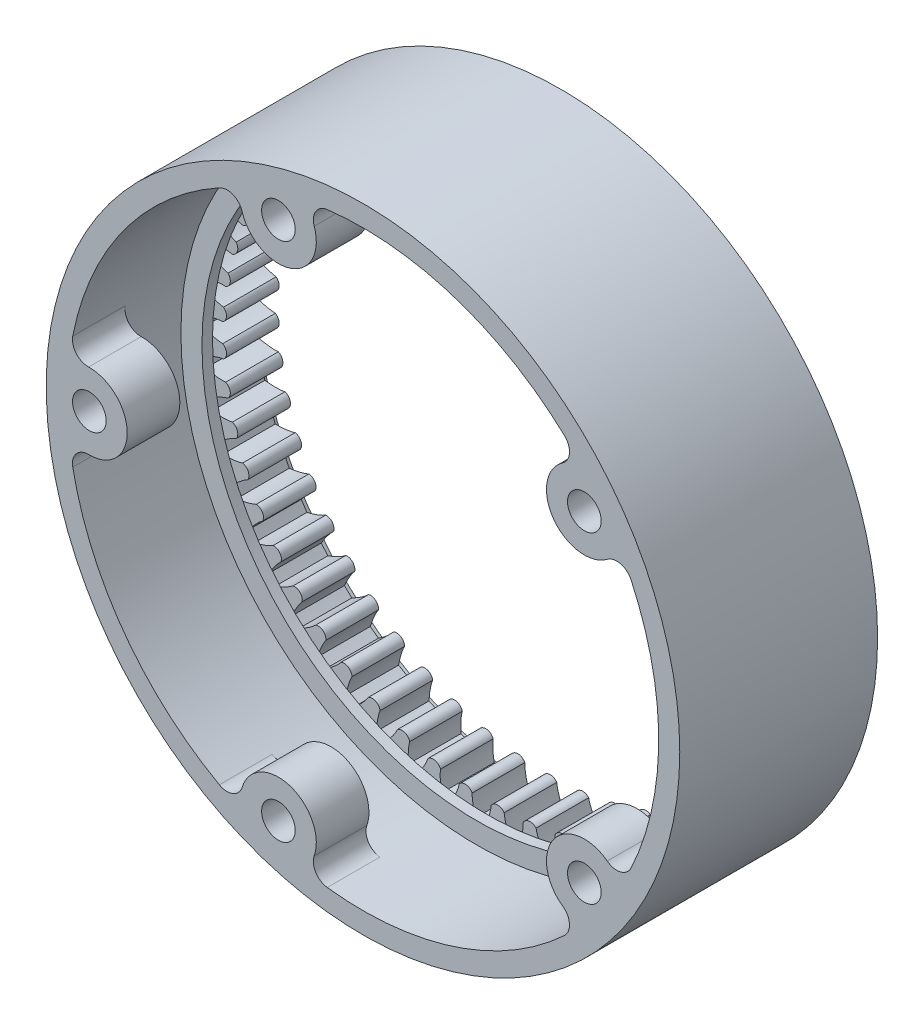
SolidWorks part; units mm, degrees
ref_plane "Front Plane" through (0, 0, 0) normal (0, 0, 1) x (1, 0, 0)
ref_plane "Top Plane" through (0, 0, 0) normal (0, 1, 0) x (1, 0, 0)
ref_plane "Right Plane" through (0, 0, 0) normal (1, 0, 0) x (0, 0, -1)
ref_plane "Plane1" through (0, 0, 15.8) normal (0, 0, 1) x (1, 0, 0)
sketch "Sketch1" plane through (0, 0, 15.8) normal (0, 0, 1) x (1, 0, 0)
  line L0 (4, 29.833) -> (4, 34.1)
  line L1 (-4, 34.1) -> (-4, 29.833)
  line L2 (-29.833, 4) -> (-34.1, 4)
  line L3 (-34.1, -4) -> (-29.833, -4)
  line L4 (-4, -29.833) -> (-4, -34.1)
  line L5 (4, -34.1) -> (4, -29.833)
  line L6 (29.833, -4) -> (34.1, -4)
  line L7 (34.1, 4) -> (29.833, 4)
  arc A0 (29.833, 4) -> (4, 29.833) centre (0, 0) ccw
  arc A1 (4, 34.1) -> (-4, 34.1) centre (0, 34.1) ccw
  arc A2 (-4, 29.833) -> (-29.833, 4) centre (0, 0) ccw
  arc A3 (-34.1, 4) -> (-34.1, -4) centre (-34.1, 0) ccw
  arc A4 (-29.833, -4) -> (-4, -29.833) centre (0, 0) ccw
  arc A5 (-4, -34.1) -> (4, -34.1) centre (0, -34.1) ccw
  arc A6 (4, -29.833) -> (29.833, -4) centre (0, 0) ccw
  arc A7 (34.1, -4) -> (34.1, 4) centre (34.1, 0) ccw
extrude "Boss-Extrude1" add sketch "Sketch1" against normal blind 1.9
sketch "Sketch2" plane through (0, 0, 13.9) normal (0, 0, -1) x (-1, 0, 0)
  line L0 (-29.833, -4) -> (-34.1, -4)
  line L1 (-34.1, 4) -> (-29.833, 4)
  arc A0 (-29.833, 4) -> (-29.833, -4) centre (0, 0) cw
  arc A1 (-34.1, -4) -> (-34.1, 4) centre (-34.1, 0) cw
extrude "Boss-Extrude2" add sketch "Sketch2" along normal blind 12.9
sketch "Sketch3" plane through (0, 0, 1) normal (0, 0, -1) x (-1, 0, 0)
  circle A0 centre (0, 0) radius 29
extrude "Cut-Extrude1" cut sketch "Sketch3" against normal blind 1
sketch "Sketch4" plane through (0, 0, 2) normal (0, 0, -1) x (-1, 0, 0)
  arc A0 (-27.9958, 0.4841) -> (-27.9958, -0.4838) centre (0, 0.0002) ccw
  arc A1 (-26.1243, -0.905) -> (-26.0527, -2.1336) centre (-26.5165, -1.5442) cw
  arc A2 (-27.8627, -2.7692) -> (-27.7503, -3.7306) centre (0, 0.0002) ccw
  arc A3 (-25.8426, -3.9317) -> (-25.6288, -5.1437) centre (-26.1579, -4.6122) cw
  arc A4 (-27.3528, -5.9852) -> (-27.1295, -6.927) centre (0, 0.0002) ccw
  arc A5 (-25.2114, -6.9052) -> (-24.8584, -8.0843) centre (-25.4456, -7.6177) cw
  arc A6 (-26.4729, -9.1202) -> (-26.1419, -10.0297) centre (0, 0.0002) ccw
  arc A7 (-24.2392, -9.7854) -> (-23.7517, -10.9155) centre (-24.3891, -10.5203) cw
  arc A8 (-25.2351, -12.1318) -> (-24.8007, -12.9968) centre (0, 0.0002) ccw
  arc A9 (-22.9393, -12.5333) -> (-22.3239, -13.5991) centre (-23.0029, -13.2806) cw
  arc A10 (-23.6561, -14.9794) -> (-23.1242, -15.7881) centre (0, 0.0002) ccw
  arc A11 (-21.3291, -15.1116) -> (-20.5942, -16.0988) centre (-21.3055, -15.8612) cw
  arc A12 (-21.7571, -17.6244) -> (-21.1349, -18.3659) centre (0, 0.0002) ccw
  arc A13 (-19.4306, -17.4856) -> (-18.5859, -18.3808) centre (-19.3201, -18.2274) cw
  arc A14 (-19.5639, -20.0311) -> (-18.8598, -20.6953) centre (0, 0.0002) ccw
  arc A15 (-17.2692, -19.6231) -> (-16.3264, -20.4142) centre (-17.0733, -20.3471) cw
  arc A16 (-17.1061, -22.1669) -> (-16.3297, -22.7449) centre (0, 0.0002) ccw
  arc A17 (-14.8743, -21.4953) -> (-13.846, -22.1716) centre (-14.5957, -22.1916) cw
  arc A18 (-14.417, -24.0029) -> (-13.5788, -24.4869) centre (0, 0.0002) ccw
  arc A19 (-12.2783, -23.0767) -> (-11.1784, -23.6291) centre (-11.9207, -23.736) cw
  arc A20 (-11.5329, -25.5143) -> (-10.6442, -25.8977) centre (0, 0.0002) ccw
  arc A21 (-9.5162, -24.3461) -> (-8.3596, -24.767) centre (-9.0845, -24.9594) cw
  arc A22 (-8.4929, -26.6807) -> (-7.5656, -26.9583) centre (0, 0.0002) ccw
  arc A23 (-6.6254, -25.2863) -> (-5.4278, -25.5701) centre (-6.1254, -25.8453) cw
  arc A24 (-5.338, -27.4863) -> (-4.3848, -27.6543) centre (0, 0.0002) ccw
  arc A25 (-3.645, -25.8844) -> (-2.4226, -26.0273) centre (-3.0835, -26.3817) cw
  arc A26 (-2.1109, -27.9201) -> (-1.1446, -27.9764) centre (0, 0.0002) ccw
  arc A27 (-0.6153, -26.1326) -> (0.6154, -26.1326) centre (0.0001, -26.5613) cw
  arc A28 (1.1447, -27.9764) -> (2.111, -27.9201) centre (0, 0.0002) ccw
  arc A29 (2.4226, -26.0273) -> (3.6451, -25.8844) centre (3.0836, -26.3817) cw
  arc A30 (4.3849, -27.6543) -> (5.3381, -27.4863) centre (0, 0.0002) ccw
  arc A31 (5.4279, -25.5701) -> (6.6255, -25.2862) centre (6.1255, -25.8453) cw
  arc A32 (7.5657, -26.9583) -> (8.4929, -26.6807) centre (0, 0.0002) ccw
  arc A33 (8.3597, -24.7671) -> (9.5162, -24.3461) centre (9.0846, -24.9594) cw
  arc A34 (10.6442, -25.8977) -> (11.533, -25.5143) centre (0, 0.0002) ccw
  arc A35 (11.1785, -23.6291) -> (12.2783, -23.0767) centre (11.9208, -23.736) cw
  arc A36 (13.5788, -24.4869) -> (14.4171, -24.0029) centre (0, 0.0002) ccw
  arc A37 (13.8461, -22.1716) -> (14.8744, -21.4952) centre (14.5958, -22.1916) cw
  arc A38 (16.3298, -22.7449) -> (17.1062, -22.1669) centre (0, 0.0002) ccw
  arc A39 (16.3265, -20.4142) -> (17.2693, -19.6231) centre (17.0734, -20.3471) cw
  arc A40 (18.8599, -20.6953) -> (19.5639, -20.0311) centre (0, 0.0002) ccw
  arc A41 (18.586, -18.3808) -> (19.4306, -17.4856) centre (19.3202, -18.2274) cw
  arc A42 (21.135, -18.3659) -> (21.7572, -17.6245) centre (0, 0.0002) ccw
  arc A43 (20.5943, -16.0988) -> (21.3292, -15.1116) centre (21.3056, -15.8612) cw
  arc A44 (23.1243, -15.7881) -> (23.6561, -14.9794) centre (0, 0.0002) ccw
  arc A45 (22.324, -13.5991) -> (22.9394, -12.5332) centre (23.0029, -13.2805) cw
  arc A46 (24.8008, -12.9968) -> (25.2352, -12.1318) centre (0, 0.0002) ccw
  arc A47 (23.7518, -10.9155) -> (24.2393, -9.7854) centre (24.3892, -10.5203) cw
  arc A48 (26.142, -10.0297) -> (26.473, -9.1202) centre (0, 0.0002) ccw
  arc A49 (24.8585, -8.0843) -> (25.2114, -6.9052) centre (25.4456, -7.6177) cw
  arc A50 (27.1296, -6.927) -> (27.3528, -5.9854) centre (0, 0.0002) ccw
  arc A51 (25.6289, -5.1439) -> (25.8426, -3.9319) centre (26.1579, -4.6123) cw
  arc A52 (27.7504, -3.7308) -> (27.8627, -2.7693) centre (0, 0.0002) ccw
  arc A53 (26.0528, -2.1336) -> (26.1244, -0.905) centre (26.5166, -1.5442) cw
  arc A54 (27.9959, -0.4838) -> (27.9959, 0.4841) centre (0, 0.0002) ccw
  arc A55 (26.1244, 0.9053) -> (26.0528, 2.134) centre (26.5166, 1.5446) cw
  arc A56 (27.8627, 2.7696) -> (27.7504, 3.731) centre (0, 0.0002) ccw
  arc A57 (25.8427, 3.9321) -> (25.6289, 5.1441) centre (26.158, 4.6125) cw
  arc A58 (27.3528, 5.9856) -> (27.1296, 6.9274) centre (0, 0.0002) ccw
  arc A59 (25.2115, 6.9056) -> (24.8584, 8.0847) centre (25.4456, 7.6181) cw
  arc A60 (26.473, 9.1206) -> (26.142, 10.0301) centre (0, 0.0002) ccw
  arc A61 (24.2393, 9.7858) -> (23.7518, 10.9159) centre (24.3892, 10.5207) cw
  arc A62 (25.2352, 12.1322) -> (24.8008, 12.9972) centre (0, 0.0002) ccw
  arc A63 (22.9394, 12.5336) -> (22.324, 13.5995) centre (23.0029, 13.2809) cw
  arc A64 (23.6561, 14.9798) -> (23.1243, 15.7885) centre (0, 0.0002) ccw
  arc A65 (21.3292, 15.112) -> (20.5942, 16.0992) centre (21.3056, 15.8616) cw
  arc A66 (21.7572, 17.6248) -> (21.135, 18.3663) centre (0, 0.0002) ccw
  arc A67 (19.4306, 17.486) -> (18.586, 18.3812) centre (19.3201, 18.2278) cw
  arc A68 (19.564, 20.0315) -> (18.8599, 20.6957) centre (0, 0.0002) ccw
  arc A69 (17.2693, 19.6235) -> (16.3264, 20.4146) centre (17.0734, 20.3475) cw
  arc A70 (17.1062, 22.1673) -> (16.3298, 22.7453) centre (0, 0.0002) ccw
  arc A71 (14.8744, 21.4956) -> (13.8461, 22.1719) centre (14.5958, 22.192) cw
  arc A72 (14.4171, 24.0033) -> (13.5788, 24.4873) centre (0, 0.0002) ccw
  arc A73 (12.2783, 23.0771) -> (11.1785, 23.6294) centre (11.9208, 23.7364) cw
  arc A74 (11.533, 25.5147) -> (10.6443, 25.8981) centre (0, 0.0002) ccw
  arc A75 (9.5162, 24.3465) -> (8.3597, 24.7674) centre (9.0846, 24.9598) cw
  arc A76 (8.493, 26.6811) -> (7.5657, 26.9587) centre (0, 0.0002) ccw
  arc A77 (6.6255, 25.2866) -> (5.4279, 25.5704) centre (6.1255, 25.8457) cw
  arc A78 (5.3381, 27.4866) -> (4.3849, 27.6547) centre (0, 0.0002) ccw
  arc A79 (3.6451, 25.8848) -> (2.4226, 26.0277) centre (3.0836, 26.382) cw
  arc A80 (2.111, 27.9205) -> (1.1447, 27.9768) centre (0, 0.0002) ccw
  arc A81 (0.6154, 26.133) -> (-0.6153, 26.1329) centre (0, 26.5616) cw
  arc A82 (-1.1446, 27.9768) -> (-2.1109, 27.9205) centre (0, 0.0002) ccw
  arc A83 (-2.4226, 26.0277) -> (-3.645, 25.8848) centre (-3.0836, 26.382) cw
  arc A84 (-4.3848, 27.6547) -> (-5.338, 27.4867) centre (0, 0.0002) ccw
  arc A85 (-5.4278, 25.5705) -> (-6.6254, 25.2866) centre (-6.1255, 25.8457) cw
  arc A86 (-7.5656, 26.9587) -> (-8.4929, 26.6811) centre (0, 0.0002) ccw
  arc A87 (-8.3596, 24.7674) -> (-9.5162, 24.3465) centre (-9.0845, 24.9598) cw
  arc A88 (-10.6442, 25.8981) -> (-11.5329, 25.5147) centre (0, 0.0002) ccw
  arc A89 (-11.1784, 23.6295) -> (-12.2782, 23.0771) centre (-11.9207, 23.7364) cw
  arc A90 (-13.5788, 24.4873) -> (-14.417, 24.0033) centre (0, 0.0002) ccw
  arc A91 (-13.846, 22.172) -> (-14.8743, 21.4956) centre (-14.5957, 22.192) cw
  arc A92 (-16.3297, 22.7453) -> (-17.1061, 22.1673) centre (0, 0.0002) ccw
  arc A93 (-16.3264, 20.4146) -> (-17.2692, 19.6235) centre (-17.0733, 20.3474) cw
  arc A94 (-18.8598, 20.6957) -> (-19.5639, 20.0315) centre (0, 0.0002) ccw
  arc A95 (-18.5859, 18.3812) -> (-19.4305, 17.486) centre (-19.3201, 18.2278) cw
  arc A96 (-21.1349, 18.3663) -> (-21.7571, 17.6248) centre (0, 0.0002) ccw
  arc A97 (-20.5942, 16.0992) -> (-21.3291, 15.112) centre (-21.3055, 15.8616) cw
  arc A98 (-23.1242, 15.7885) -> (-23.6561, 14.9798) centre (0, 0.0002) ccw
  arc A99 (-22.3239, 13.5995) -> (-22.9393, 12.5336) centre (-23.0029, 13.2809) cw
  arc A100 (-24.8007, 12.9972) -> (-25.2351, 12.1322) centre (0, 0.0002) ccw
  arc A101 (-23.7518, 10.9159) -> (-24.2392, 9.7858) centre (-24.3891, 10.5206) cw
  arc A102 (-26.1419, 10.0301) -> (-26.4729, 9.1206) centre (0, 0.0002) ccw
  arc A103 (-24.8584, 8.0847) -> (-25.2113, 6.9056) centre (-25.4456, 7.6181) cw
  arc A104 (-27.1295, 6.9274) -> (-27.3528, 5.9856) centre (0, 0.0002) ccw
  arc A105 (-25.6289, 5.1441) -> (-25.8425, 3.9321) centre (-26.1579, 4.6125) cw
  arc A106 (-27.7503, 3.731) -> (-27.8627, 2.7696) centre (0, 0.0002) ccw
  arc A107 (-26.0527, 2.134) -> (-26.1243, 0.9053) centre (-26.5165, 1.5446) cw
  ellipse E0 centre (-27.7817, 0.0692) end of major axis (-29.975, 0.8686) minor radius 0.5928 (-27.9958, -0.4838) -> (-26.1243, -0.905) ccw
  ellipse E1 centre (-27.576, -3.281) end of major axis (-29.647, -4.3182) minor radius 0.586 (-26.0527, -2.1336) -> (-27.8627, -2.7692) ccw
  ellipse E2 centre (-27.6019, -3.1565) end of major axis (-29.8731, -2.6172) minor radius 0.5928 (-27.7503, -3.7306) -> (-25.8426, -3.9317) ccw
  ellipse E3 centre (-27.0086, -6.4602) end of major axis (-28.9452, -7.7308) minor radius 0.586 (-25.6288, -5.1437) -> (-27.3528, -5.9852) ccw
  ellipse E4 centre (-27.0488, -6.3396) end of major axis (-29.3673, -6.0675) minor radius 0.5928 (-27.1295, -6.927) -> (-25.2114, -6.9052) ccw
  ellipse E5 centre (-26.076, -9.552) end of major axis (-27.8519, -11.0388) minor radius 0.586 (-24.8584, -8.0843) -> (-26.4729, -9.1202) ccw
  ellipse E6 centre (-26.1299, -9.4369) end of major axis (-28.4643, -9.4359) minor radius 0.5928 (-26.1419, -10.0297) -> (-24.2392, -9.7854) ccw
  ellipse E7 centre (-24.7907, -12.5146) end of major axis (-23.1993, -10.8317) minor radius 0.586 (-23.7517, -10.9155) -> (-25.2351, -12.1318) ccw
  ellipse E8 centre (-24.8576, -12.4066) end of major axis (-27.1764, -12.6766) minor radius 0.5928 (-24.8007, -12.9968) -> (-22.9393, -12.5333) ccw
  ellipse E9 centre (-23.1702, -15.308) end of major axis (-21.785, -13.4517) minor radius 0.586 (-22.3239, -13.5991) -> (-23.6561, -14.9794) ccw
  ellipse E10 centre (-23.2492, -15.2085) end of major axis (-25.5209, -15.7458) minor radius 0.5928 (-23.1242, -15.7881) -> (-21.3291, -15.1116) ccw
  ellipse E11 centre (-21.2363, -17.8944) end of major axis (-20.076, -15.8898) minor radius 0.586 (-20.5942, -16.0988) -> (-21.7571, -17.6244) ccw
  ellipse E12 centre (-21.3264, -17.8047) end of major axis (-23.5204, -18.6022) minor radius 0.5928 (-21.1349, -18.3659) -> (-19.4306, -17.4856) ccw
  ellipse E13 centre (-19.0153, -20.2388) end of major axis (-18.0955, -18.1131) minor radius 0.586 (-18.5859, -18.3808) -> (-19.5639, -20.0311) ccw
  ellipse E14 centre (-19.1151, -20.1602) end of major axis (-21.2017, -21.2069) minor radius 0.5928 (-18.8598, -20.6953) -> (-17.2692, -19.6231) ccw
  ellipse E15 centre (-16.5371, -22.3095) end of major axis (-15.8703, -20.0914) minor radius 0.586 (-16.3264, -20.4142) -> (-17.1061, -22.1669) ccw
  ellipse E16 centre (-16.6454, -22.243) end of major axis (-18.5964, -23.5249) minor radius 0.5928 (-16.3297, -22.7449) -> (-14.8743, -21.4953) ccw
  ellipse E17 centre (-13.8353, -24.0785) end of major axis (-13.4306, -21.798) minor radius 0.586 (-13.846, -22.1716) -> (-14.417, -24.0029) ccw
  ellipse E18 centre (-13.9506, -24.025) end of major axis (-15.7395, -25.5247) minor radius 0.5928 (-13.5788, -24.4869) -> (-12.2783, -23.0767) ccw
  ellipse E19 centre (-10.9464, -25.5219) end of major axis (-10.8091, -23.2098) minor radius 0.586 (-11.1784, -23.6291) -> (-11.5329, -25.5143) ccw
  ellipse E20 centre (-11.0671, -25.4821) end of major axis (-9.4644, -23.7849) minor radius 0.5928 (-10.6442, -25.8977) -> (-9.5162, -24.3461) ccw
  ellipse E21 centre (-7.9094, -26.6201) end of major axis (-8.0415, -24.3077) minor radius 0.586 (-8.3596, -24.767) -> (-8.4929, -26.6807) ccw
  ellipse E22 centre (-8.034, -26.5947) end of major axis (-6.6391, -24.7228) minor radius 0.5928 (-7.5656, -26.9583) -> (-6.6254, -25.2863) ccw
  ellipse E23 centre (-4.7655, -27.3584) end of major axis (-5.1652, -25.0769) minor radius 0.586 (-5.4278, -25.5701) -> (-5.338, -27.4863) ccw
  ellipse E24 centre (-4.8922, -27.3475) end of major axis (-3.724, -25.3264) minor radius 0.5928 (-4.3848, -27.6543) -> (-3.645, -25.8844) ccw
  ellipse E25 centre (-1.5572, -27.7266) end of major axis (-2.219, -25.507) minor radius 0.586 (-2.4226, -26.0273) -> (-2.1109, -27.9201) ccw
  ellipse E26 centre (-1.6842, -27.7306) end of major axis (-0.7586, -25.5875) minor radius 0.5928 (-1.1446, -27.9764) -> (-0.6153, -26.1326) ccw
  ellipse E27 centre (1.6722, -27.7199) end of major axis (0.7572, -25.5921) minor radius 0.586 (0.6154, -26.1326) -> (1.1447, -27.9764) ccw
  ellipse E28 centre (1.5465, -27.7386) end of major axis (2.217, -25.5026) minor radius 0.5928 (2.111, -27.9201) -> (2.4226, -26.0273) ccw
  ellipse E29 centre (4.879, -27.3384) end of major axis (6.0349, -29.3456) minor radius 0.586 (3.6451, -25.8844) -> (4.3849, -27.6543) ccw
  ellipse E30 centre (4.7563, -27.3715) end of major axis (5.1627, -25.0727) minor radius 0.5928 (5.3381, -27.4863) -> (5.4279, -25.5701) ccw
  ellipse E31 centre (8.0199, -26.5871) end of major axis (6.6388, -24.7277) minor radius 0.586 (6.6255, -25.2862) -> (7.5657, -26.9583) ccw
  ellipse E32 centre (7.9018, -26.6342) end of major axis (8.0386, -24.3038) minor radius 0.5928 (8.4929, -26.6807) -> (8.3597, -24.7671) ccw
  ellipse E33 centre (11.0522, -25.4763) end of major axis (9.4646, -23.7898) minor radius 0.586 (9.5162, -24.3461) -> (10.6442, -25.8977) ccw
  ellipse E34 centre (10.9405, -25.5368) end of major axis (10.8058, -23.2063) minor radius 0.5928 (11.533, -25.5143) -> (11.1785, -23.6291) ccw
  ellipse E35 centre (13.9351, -24.0209) end of major axis (15.7078, -25.5118) minor radius 0.586 (12.2783, -23.0767) -> (13.5788, -24.4869) ccw
  ellipse E36 centre (13.8312, -24.094) end of major axis (13.4268, -21.7949) minor radius 0.5928 (14.4171, -24.0029) -> (13.8461, -22.1716) ccw
  ellipse E37 centre (16.6296, -22.2407) end of major axis (14.6959, -20.9658) minor radius 0.586 (14.8744, -21.4952) -> (16.3298, -22.7449) ccw
  ellipse E38 centre (16.5348, -22.3254) end of major axis (15.8663, -20.0888) minor radius 0.5928 (17.1062, -22.1669) -> (16.3265, -20.4142) ccw
  ellipse E39 centre (19.0992, -20.1598) end of major axis (17.0305, -19.118) minor radius 0.586 (17.2693, -19.6231) -> (18.8599, -20.6953) ccw
  ellipse E40 centre (19.0149, -20.2549) end of major axis (18.0912, -18.111) minor radius 0.5928 (19.5639, -20.0311) -> (18.586, -18.3808) ccw
  ellipse E41 centre (21.3105, -17.8062) end of major axis (19.1348, -17.0116) minor radius 0.586 (19.4306, -17.4856) -> (21.135, -18.3659) ccw
  ellipse E42 centre (21.2378, -17.9104) end of major axis (20.0715, -15.8883) minor radius 0.5928 (21.7572, -17.6245) -> (20.5943, -16.0988) ccw
  ellipse E43 centre (23.2336, -15.2118) end of major axis (20.9804, -14.6751) minor radius 0.586 (21.3292, -15.1116) -> (23.1243, -15.7881) ccw
  ellipse E44 centre (23.1735, -15.3238) end of major axis (21.7803, -13.4507) minor radius 0.5928 (23.6561, -14.9794) -> (22.324, -13.5991) ccw
  ellipse E45 centre (24.8425, -12.4117) end of major axis (22.5422, -12.1402) minor radius 0.586 (22.9394, -12.5332) -> (24.8008, -12.9968) ccw
  ellipse E46 centre (24.7958, -12.5299) end of major axis (23.1946, -10.8312) minor radius 0.5928 (25.2352, -12.1318) -> (23.7518, -10.9155) ccw
  ellipse E47 centre (26.1154, -9.4437) end of major axis (23.7992, -9.4412) minor radius 0.586 (24.2393, -9.7854) -> (26.142, -10.0297) ccw
  ellipse E48 centre (26.0828, -9.5666) end of major axis (24.2952, -8.0652) minor radius 0.5928 (26.473, -9.1202) -> (24.8585, -8.0843) ccw
  ellipse E49 centre (27.0352, -6.3481) end of major axis (24.7344, -6.6144) minor radius 0.586 (25.2114, -6.9052) -> (27.1296, -6.927) ccw
  ellipse E50 centre (27.017, -6.4741) end of major axis (25.0672, -5.1904) minor radius 0.5928 (27.3528, -5.9854) -> (25.6289, -5.1439) ccw
  ellipse E51 centre (27.5894, -3.1668) end of major axis (25.335, -3.6984) minor radius 0.586 (25.8426, -3.9319) -> (27.7504, -3.7308) ccw
  ellipse E52 centre (27.5859, -3.2936) end of major axis (25.5003, -2.245) minor radius 0.5928 (27.8627, -2.7693) -> (26.0528, -2.1336) ccw
  ellipse E53 centre (27.7705, 0.0578) end of major axis (25.5931, -0.732) minor radius 0.586 (26.1244, -0.905) -> (27.9959, -0.4838) ccw
  ellipse E54 centre (27.7818, -0.0688) end of major axis (29.9751, -0.8682) minor radius 0.5928 (27.9959, 0.4841) -> (26.1244, 0.9053) ccw
  ellipse E55 centre (27.576, 3.2813) end of major axis (25.505, 2.2442) minor radius 0.586 (26.0528, 2.134) -> (27.8627, 2.7696) ccw
  ellipse E56 centre (27.602, 3.1569) end of major axis (25.3307, 3.6963) minor radius 0.5928 (27.7504, 3.731) -> (25.8427, 3.9321) ccw
  ellipse E57 centre (27.0087, 6.4605) end of major axis (25.0721, 5.1899) minor radius 0.586 (25.6289, 5.1441) -> (27.3528, 5.9856) ccw
  ellipse E58 centre (27.0489, 6.34) end of major axis (24.7304, 6.612) minor radius 0.5928 (27.1296, 6.9274) -> (25.2115, 6.9056) ccw
  ellipse E59 centre (26.076, 9.5524) end of major axis (24.3001, 8.0655) minor radius 0.586 (24.8584, 8.0847) -> (26.473, 9.1206) ccw
  ellipse E60 centre (26.13, 9.4373) end of major axis (23.7956, 9.4383) minor radius 0.5928 (26.142, 10.0301) -> (24.2393, 9.7858) ccw
  ellipse E61 centre (24.7908, 12.515) end of major axis (26.3821, 14.198) minor radius 0.586 (23.7518, 10.9159) -> (25.2352, 12.1322) ccw
  ellipse E62 centre (24.8577, 12.407) end of major axis (22.539, 12.137) minor radius 0.5928 (24.8008, 12.9972) -> (22.9394, 12.5336) ccw
  ellipse E63 centre (23.1703, 15.3084) end of major axis (24.5555, 17.1648) minor radius 0.586 (22.324, 13.5995) -> (23.6561, 14.9798) ccw
  ellipse E64 centre (23.2493, 15.2089) end of major axis (25.521, 15.7462) minor radius 0.5928 (23.1243, 15.7885) -> (21.3292, 15.112) ccw
  ellipse E65 centre (21.2364, 17.8948) end of major axis (22.3968, 19.8994) minor radius 0.586 (20.5942, 16.0992) -> (21.7572, 17.6248) ccw
  ellipse E66 centre (21.3265, 17.8051) end of major axis (19.1325, 17.0077) minor radius 0.5928 (21.135, 18.3663) -> (19.4306, 17.486) ccw
  ellipse E67 centre (19.0154, 20.2392) end of major axis (19.9352, 22.365) minor radius 0.586 (18.586, 18.3812) -> (19.564, 20.0315) ccw
  ellipse E68 centre (19.1152, 20.1606) end of major axis (17.0287, 19.1138) minor radius 0.5928 (18.8599, 20.6957) -> (17.2693, 19.6235) ccw
  ellipse E69 centre (16.5372, 22.3099) end of major axis (17.204, 24.5281) minor radius 0.586 (16.3264, 20.4146) -> (17.1062, 22.1673) ccw
  ellipse E70 centre (16.6455, 22.2434) end of major axis (14.6946, 20.9615) minor radius 0.5928 (16.3298, 22.7453) -> (14.8744, 21.4956) ccw
  ellipse E71 centre (13.8354, 24.0789) end of major axis (14.2402, 26.3595) minor radius 0.586 (13.8461, 22.1719) -> (14.4171, 24.0033) ccw
  ellipse E72 centre (13.9507, 24.0254) end of major axis (12.1617, 22.5257) minor radius 0.5928 (13.5788, 24.4873) -> (12.2783, 23.0771) ccw
  ellipse E73 centre (10.9465, 25.5223) end of major axis (11.0837, 27.8344) minor radius 0.586 (11.1785, 23.6294) -> (11.533, 25.5147) ccw
  ellipse E74 centre (11.0672, 25.4825) end of major axis (12.6699, 27.1798) minor radius 0.5928 (10.6443, 25.8981) -> (9.5162, 24.3465) ccw
  ellipse E75 centre (7.9095, 26.6205) end of major axis (7.7774, 28.933) minor radius 0.586 (8.3597, 24.7674) -> (8.493, 26.6811) ccw
  ellipse E76 centre (8.034, 26.595) end of major axis (9.4289, 28.4669) minor radius 0.5928 (7.5657, 26.9587) -> (6.6255, 25.2866) ccw
  ellipse E77 centre (4.7656, 27.3588) end of major axis (4.366, 29.6402) minor radius 0.586 (5.4279, 25.5704) -> (5.3381, 27.4866) ccw
  ellipse E78 centre (4.8922, 27.3479) end of major axis (6.0603, 29.369) minor radius 0.5928 (4.3849, 27.6547) -> (3.6451, 25.8848) ccw
  ellipse E79 centre (1.5573, 27.727) end of major axis (0.8954, 29.9467) minor radius 0.586 (2.4226, 26.0277) -> (2.111, 27.9205) ccw
  ellipse E80 centre (1.6843, 27.7309) end of major axis (2.6099, 29.874) minor radius 0.5928 (1.1447, 27.9768) -> (0.6154, 26.133) ccw
  ellipse E81 centre (-1.6722, 27.7203) end of major axis (-2.5872, 29.8481) minor radius 0.586 (-0.6153, 26.1329) -> (-1.1446, 27.9768) ccw
  ellipse E82 centre (-1.5464, 27.739) end of major axis (-0.8759, 29.975) minor radius 0.5928 (-2.1109, 27.9205) -> (-2.4226, 26.0277) ccw
  ellipse E83 centre (-4.879, 27.3387) end of major axis (-6.0348, 29.3459) minor radius 0.586 (-3.645, 25.8848) -> (-4.3848, 27.6547) ccw
  ellipse E84 centre (-4.7563, 27.3719) end of major axis (-4.3499, 29.6706) minor radius 0.5928 (-5.338, 27.4867) -> (-5.4278, 25.5705) ccw
  ellipse E85 centre (-8.0198, 26.5875) end of major axis (-9.4008, 28.4469) minor radius 0.586 (-6.6254, 25.2866) -> (-7.5656, 26.9587) ccw
  ellipse E86 centre (-7.9018, 26.6346) end of major axis (-7.765, 28.965) minor radius 0.5928 (-8.4929, 26.6811) -> (-8.3596, 24.7674) ccw
  ellipse E87 centre (-11.0522, 25.4767) end of major axis (-12.6397, 27.1632) minor radius 0.586 (-9.5162, 24.3465) -> (-10.6442, 25.8981) ccw
  ellipse E88 centre (-10.9404, 25.5372) end of major axis (-11.0751, 27.8677) minor radius 0.5928 (-11.5329, 25.5147) -> (-11.1784, 23.6295) ccw
  ellipse E89 centre (-13.9351, 24.0213) end of major axis (-12.1624, 22.5305) minor radius 0.586 (-12.2782, 23.0771) -> (-13.5788, 24.4873) ccw
  ellipse E90 centre (-13.8311, 24.0944) end of major axis (-14.2354, 26.3935) minor radius 0.5928 (-14.417, 24.0033) -> (-13.846, 22.172) ccw
  ellipse E91 centre (-16.6295, 22.2411) end of major axis (-18.5633, 23.5161) minor radius 0.586 (-14.8743, 21.4956) -> (-16.3297, 22.7453) ccw
  ellipse E92 centre (-16.5347, 22.3258) end of major axis (-17.2032, 24.5624) minor radius 0.5928 (-17.1061, 22.1673) -> (-16.3264, 20.4146) ccw
  ellipse E93 centre (-19.0991, 20.1602) end of major axis (-21.1678, 21.202) minor radius 0.586 (-17.2692, 19.6235) -> (-18.8598, 20.6957) ccw
  ellipse E94 centre (-19.0148, 20.2553) end of major axis (-19.9384, 22.3992) minor radius 0.5928 (-19.5639, 20.0315) -> (-18.5859, 18.3812) ccw
  ellipse E95 centre (-21.3104, 17.8066) end of major axis (-23.486, 18.6012) minor radius 0.586 (-19.4305, 17.486) -> (-21.1349, 18.3663) ccw
  ellipse E96 centre (-21.2377, 17.9108) end of major axis (-22.404, 19.933) minor radius 0.5928 (-21.7571, 17.6248) -> (-20.5942, 16.0992) ccw
  ellipse E97 centre (-23.2335, 15.2122) end of major axis (-25.4867, 15.7489) minor radius 0.586 (-21.3291, 15.112) -> (-23.1242, 15.7885) ccw
  ellipse E98 centre (-23.1734, 15.3242) end of major axis (-24.5665, 17.1973) minor radius 0.5928 (-23.6561, 14.9798) -> (-22.3239, 13.5995) ccw
  ellipse E99 centre (-24.8424, 12.4121) end of major axis (-27.1426, 12.6836) minor radius 0.586 (-22.9393, 12.5336) -> (-24.8007, 12.9972) ccw
  ellipse E100 centre (-24.7957, 12.5303) end of major axis (-26.3969, 14.229) minor radius 0.5928 (-25.2351, 12.1322) -> (-23.7518, 10.9159) ccw
  ellipse E101 centre (-26.1153, 9.4441) end of major axis (-28.4316, 9.4467) minor radius 0.586 (-24.2392, 9.7858) -> (-26.1419, 10.0301) ccw
  ellipse E102 centre (-26.0827, 9.5669) end of major axis (-27.8703, 11.0683) minor radius 0.5928 (-26.4729, 9.1206) -> (-24.8584, 8.0847) ccw
  ellipse E103 centre (-27.0351, 6.3485) end of major axis (-29.336, 6.0821) minor radius 0.586 (-25.2113, 6.9056) -> (-27.1295, 6.9274) ccw
  ellipse E104 centre (-27.0169, 6.4742) end of major axis (-28.9667, 7.7579) minor radius 0.5928 (-27.3528, 5.9856) -> (-25.6289, 5.1441) ccw
  ellipse E105 centre (-27.5893, 3.1669) end of major axis (-29.8437, 2.6353) minor radius 0.586 (-25.8425, 3.9321) -> (-27.7503, 3.731) ccw
  ellipse E106 centre (-27.5859, 3.294) end of major axis (-29.6715, 4.3426) minor radius 0.5928 (-27.8627, 2.7696) -> (-26.0527, 2.134) ccw
  ellipse E107 centre (-27.7704, -0.0574) end of major axis (-29.9478, -0.8472) minor radius 0.586 (-26.1243, 0.9053) -> (-27.9958, 0.4841) ccw
  point P3 (-27.7818, 0.069)
  point P4 (-29.975, 0.8684)
  point P5 (-27.5788, 0.626)
  point P6 (-27.9958, -0.484)
  point P7 (-26.1244, -0.9051)
  point P8 (-27.0757, -0.7649)
  point P9 (-28.4879, 0.9028)
  point P18 (-27.576, -3.2812)
  point P19 (-29.647, -4.3183)
  point P20 (-27.8384, -2.7572)
  point P21 (-26.0527, -2.1338)
  point P22 (-27.8627, -2.7694)
  point P23 (-26.9809, -2.3834)
  point P24 (-28.1711, -4.1789)
  point P32 (-27.6019, -3.1567)
  point P33 (-29.8732, -2.6174)
  point P34 (-27.465, -2.58)
  point P35 (-27.7503, -3.7308)
  point P36 (-25.8426, -3.9319)
  point P37 (-26.8038, -3.903)
  point P38 (-28.4001, -2.4105)
  point P47 (-27.0086, -6.4603)
  point P48 (-28.9452, -7.731)
  point P49 (-27.3301, -5.9704)
  point P50 (-25.6289, -5.1439)
  point P51 (-27.3528, -5.9854)
  point P52 (-26.5218, -5.4996)
  point P53 (-27.4955, -7.4211)
  point P61 (-27.0488, -6.3398)
  point P62 (-29.3673, -6.0677)
  point P63 (-26.9797, -5.751)
  point P64 (-27.1296, -6.9272)
  point P65 (-25.2114, -6.9054)
  point P66 (-26.1694, -6.9883)
  point P67 (-27.9282, -5.6913)
  point P76 (-26.076, -9.5522)
  point P77 (-27.852, -11.039)
  point P78 (-26.4521, -9.1029)
  point P79 (-24.8584, -8.0845)
  point P80 (-26.473, -9.1204)
  point P81 (-25.704, -8.5414)
  point P82 (-26.448, -10.5629)
  point P90 (-26.1299, -9.4371)
  point P91 (-28.4643, -9.436)
  point P92 (-26.1297, -8.8443)
  point P93 (-26.1419, -10.0299)
  point P94 (-24.2393, -9.7856)
  point P95 (-25.1812, -9.9791)
  point P96 (-27.0787, -8.895)
  point P105 (-24.7907, -12.5148)
  point P106 (-25.2165, -12.1122)
  point P107 (-23.1994, -10.8319)
  point P108 (-23.7518, -10.9157)
  point P109 (-25.2352, -12.132)
  point P110 (-24.5386, -11.4677)
  point P111 (-25.0429, -13.5619)
  point P119 (-24.8577, -12.4068)
  point P120 (-27.1764, -12.6767)
  point P121 (-24.9262, -11.8179)
  point P122 (-24.8008, -12.997)
  point P123 (-22.9394, -12.5335)
  point P124 (-23.8524, -12.835)
  point P125 (-25.8629, -11.9785)
  point P134 (-23.1702, -15.3082)
  point P135 (-23.6399, -14.9578)
  point P136 (-21.785, -13.4519)
  point P137 (-22.3239, -13.5993)
  point P138 (-23.6561, -14.9796)
  point P139 (-23.0413, -14.2389)
  point P140 (-23.2991, -16.3776)
  point P148 (-23.2492, -15.2087)
  point P149 (-25.521, -15.746)
  point P150 (-23.3857, -14.6318)
  point P151 (-23.1242, -15.7883)
  point P152 (-21.3292, -15.1118)
  point P153 (-22.2011, -15.5173)
  point P154 (-24.2974, -14.9)
  point P163 (-21.2364, -17.8946)
  point P164 (-21.7435, -17.6011)
  point P165 (-20.076, -15.89)
  point P166 (-20.5942, -16.099)
  point P167 (-21.7571, -17.6246)
  point P168 (-21.2325, -16.8176)
  point P169 (-21.2403, -18.9717)
  point P177 (-21.3264, -17.8049)
  point P178 (-23.5204, -18.6024)
  point P179 (-21.5289, -17.2478)
  point P180 (-21.135, -18.3661)
  point P181 (-19.4306, -17.4858)
  point P182 (-20.2495, -17.9898)
  point P183 (-22.4033, -17.62)
  point P192 (-19.0154, -20.239)
  point P193 (-19.5531, -20.0063)
  point P194 (-18.0956, -18.1133)
  point P195 (-18.586, -18.381)
  point P196 (-19.5639, -20.0313)
  point P197 (-19.1365, -19.1688)
  point P198 (-18.8942, -21.3092)
  point P206 (-19.1152, -20.1604)
  point P207 (-21.2018, -21.2071)
  point P208 (-19.381, -19.6305)
  point P209 (-18.8599, -20.6955)
  point P210 (-17.2692, -19.6233)
  point P211 (-18.0241, -20.219)
  point P212 (-20.2063, -20.1018)
  point P221 (-16.5372, -22.3097)
  point P222 (-17.0983, -22.141)
  point P223 (-15.8704, -20.0916)
  point P224 (-16.3264, -20.4144)
  point P225 (-17.1061, -22.1671)
  point P226 (-16.7818, -21.2608)
  point P227 (-16.2926, -23.3586)
  point P235 (-16.6455, -22.2432)
  point P236 (-18.5964, -23.5251)
  point P237 (-16.971, -21.7478)
  point P238 (-16.3298, -22.7451)
  point P239 (-14.8743, -21.4955)
  point P240 (-15.555, -22.1748)
  point P241 (-17.736, -22.3117)
  point P250 (-13.8354, -24.0787)
  point P251 (-14.4123, -23.9763)
  point P252 (-13.4306, -21.7981)
  point P253 (-13.846, -22.1717)
  point P254 (-14.417, -24.0031)
  point P255 (-14.2001, -23.0653)
  point P256 (-13.4706, -25.0922)
  point P264 (-13.9506, -24.0252)
  point P265 (-15.7396, -25.5249)
  point P266 (-14.3315, -23.5709)
  point P267 (-13.5788, -24.4871)
  point P268 (-12.2783, -23.0769)
  point P269 (-12.8755, -23.8306)
  point P270 (-15.0258, -24.2198)
  point P279 (-10.9464, -25.5221)
  point P280 (-11.5314, -25.4874)
  point P281 (-10.8092, -23.21)
  point P282 (-11.1784, -23.6293)
  point P283 (-11.5329, -25.5145)
  point P284 (-11.4263, -24.5578)
  point P285 (-10.4665, -26.4863)
  point P293 (-11.0672, -25.4823)
  point P294 (-11.4982, -25.0753)
  point P295 (-9.4644, -23.7851)
  point P296 (-10.6442, -25.8979)
  point P297 (-9.5162, -24.3463)
  point P298 (-10.0218, -25.1643)
  point P299 (-12.1125, -25.8004)
  point P308 (-7.9095, -26.6203)
  point P309 (-8.4945, -26.6537)
  point P310 (-8.0416, -24.3079)
  point P311 (-8.3597, -24.7672)
  point P312 (-8.4929, -26.6809)
  point P313 (-8.4981, -25.7183)
  point P314 (-7.3209, -27.5223)
  point P322 (-8.034, -26.5949)
  point P323 (-8.5094, -26.2406)
  point P324 (-6.6392, -24.723)
  point P325 (-7.5657, -26.9585)
  point P326 (-6.6254, -25.2865)
  point P327 (-7.0327, -26.1576)
  point P328 (-9.0353, -27.0322)
  point P337 (-4.7656, -27.3586)
  point P338 (-5.3428, -27.4597)
  point P339 (-5.1652, -25.0771)
  point P340 (-5.4278, -25.5702)
  point P341 (-5.338, -27.4865)
  point P342 (-5.4549, -26.531)
  point P343 (-4.0762, -28.1861)
  point P351 (-4.8922, -27.3477)
  point P352 (-5.4055, -27.0511)
  point P353 (-3.7241, -25.3266)
  point P354 (-4.3848, -27.6545)
  point P355 (-3.6451, -25.8846)
  point P356 (-3.9484, -26.7971)
  point P357 (-5.836, -27.8983)
  point P366 (-1.5572, -27.7268)
  point P367 (-2.1188, -27.8943)
  point P368 (-2.219, -25.5072)
  point P369 (-2.4226, -26.0275)
  point P370 (-2.1109, -27.9203)
  point P371 (-2.338, -26.9849)
  point P372 (-0.7765, -28.4688)
  point P380 (-1.6842, -27.7308)
  point P381 (-2.2285, -27.4957)
  point P382 (-0.7587, -25.5877)
  point P383 (-1.1447, -27.9766)
  point P384 (-0.6154, -26.1328)
  point P385 (-0.8108, -27.0743)
  point P386 (-2.5577, -28.3872)
  point P395 (1.6722, -27.7201)
  point P396 (1.1339, -27.9516)
  point P397 (0.7572, -25.5923)
  point P398 (0.6154, -26.1327)
  point P399 (1.1447, -27.9766)
  point P400 (0.8106, -27.0738)
  point P401 (2.5338, -28.3664)
  point P409 (1.5465, -27.7388)
  point P410 (0.9787, -27.5685)
  point P411 (2.217, -25.5028)
  point P412 (2.1109, -27.9203)
  point P413 (2.4226, -26.0275)
  point P414 (2.3379, -26.9854)
  point P415 (0.7551, -28.4922)
  point P424 (4.879, -27.3386)
  point P425 (4.3712, -27.631)
  point P426 (3.7231, -25.3314)
  point P427 (3.645, -25.8846)
  point P428 (4.3848, -27.6545)
  point P429 (3.9482, -26.7967)
  point P430 (5.8098, -27.8805)
  point P438 (4.7563, -27.3717)
  point P439 (4.1725, -27.2685)
  point P440 (5.1627, -25.0729)
  point P441 (5.338, -27.4865)
  point P442 (5.4278, -25.5703)
  point P443 (5.4549, -26.5315)
  point P444 (4.0577, -28.2119)
  point P453 (8.0198, -26.5873)
  point P454 (7.5494, -26.9367)
  point P455 (6.6388, -24.7279)
  point P456 (6.6254, -25.2864)
  point P457 (7.5657, -26.9585)
  point P458 (7.0324, -26.1571)
  point P459 (9.0073, -27.0175)
  point P467 (7.9018, -26.6344)
  point P468 (7.31, -26.5997)
  point P469 (8.0386, -24.304)
  point P470 (8.4929, -26.6809)
  point P471 (8.3597, -24.7673)
  point P472 (8.4981, -25.7188)
  point P473 (7.3055, -27.55)
  point P482 (11.0522, -25.4765)
  point P483 (10.6255, -25.8781)
  point P484 (9.4646, -23.7899)
  point P485 (9.5162, -24.3463)
  point P486 (10.6442, -25.8979)
  point P487 (10.0215, -25.1638)
  point P488 (12.0829, -25.7891)
  point P496 (10.9404, -25.537)
  point P497 (10.3486, -25.5712)
  point P498 (10.8058, -23.2065)
  point P499 (11.5329, -25.5145)
  point P500 (11.1784, -23.6293)
  point P501 (11.4264, -24.5584)
  point P502 (10.4545, -26.5156)
  point P511 (13.9351, -24.0211)
  point P512 (12.1625, -22.5303)
  point P513 (14.3123, -23.5727)
  point P514 (12.2783, -23.0769)
  point P515 (13.5788, -24.4871)
  point P516 (12.8751, -23.8303)
  point P517 (14.9951, -24.212)
  point P525 (13.8311, -24.0942)
  point P526 (13.2473, -24.1969)
  point P527 (13.4268, -21.7951)
  point P528 (14.417, -24.0031)
  point P529 (13.8461, -22.1718)
  point P530 (14.2002, -23.0658)
  point P531 (13.4621, -25.1227)
  point P540 (16.6296, -22.2409)
  point P541 (14.6958, -20.966)
  point P542 (16.9521, -21.7517)
  point P543 (14.8743, -21.4954)
  point P544 (16.3298, -22.7451)
  point P545 (15.5546, -22.1744)
  point P546 (17.7046, -22.3075)
  point P554 (16.5348, -22.3256)
  point P555 (15.9668, -22.4954)
  point P556 (15.8663, -20.089)
  point P557 (17.1061, -22.1671)
  point P558 (16.3264, -20.4144)
  point P559 (16.782, -21.2613)
  point P560 (16.2876, -23.3899)
  point P569 (19.0991, -20.16)
  point P570 (17.0305, -19.1181)
  point P571 (19.3627, -19.6366)
  point P572 (17.2692, -19.6233)
  point P573 (18.8599, -20.6955)
  point P574 (18.0237, -20.2187)
  point P575 (20.1746, -20.1012)
  point P583 (19.0148, -20.2551)
  point P584 (18.4704, -20.4896)
  point P585 (18.0912, -18.1112)
  point P586 (19.5639, -20.0313)
  point P587 (18.586, -18.381)
  point P588 (19.1368, -19.1693)
  point P589 (18.8929, -21.3409)
  point P598 (21.3104, -17.8064)
  point P599 (19.1348, -17.0118)
  point P600 (21.5115, -17.256)
  point P601 (19.4306, -17.4858)
  point P602 (21.135, -18.3661)
  point P603 (20.2491, -17.9896)
  point P604 (22.3718, -17.6232)
  point P612 (21.2377, -17.9106)
  point P613 (20.7242, -18.2068)
  point P614 (20.0714, -15.8885)
  point P615 (21.7571, -17.6246)
  point P616 (20.5942, -16.099)
  point P617 (21.2328, -16.818)
  point P618 (21.2427, -19.0033)
  point P627 (23.2335, -15.212)
  point P628 (20.9803, -14.6753)
  point P629 (23.3693, -14.642)
  point P630 (21.3292, -15.1118)
  point P631 (23.1242, -15.7883)
  point P632 (22.2006, -15.5172)
  point P633 (24.2665, -14.9068)
  point P641 (23.1734, -15.324)
  point P642 (22.6978, -15.6778)
  point P643 (21.7803, -13.4509)
  point P644 (23.6561, -14.9796)
  point P645 (22.324, -13.5993)
  point P646 (23.0417, -14.2393)
  point P647 (23.3052, -16.4087)
  point P656 (24.8424, -12.4119)
  point P657 (22.5422, -12.1404)
  point P658 (24.9111, -11.83)
  point P659 (22.9393, -12.5334)
  point P660 (24.8008, -12.997)
  point P661 (23.8519, -12.8349)
  point P662 (25.8329, -11.9889)
  point P670 (24.7957, -12.5301)
  point P671 (24.3644, -12.9367)
  point P672 (23.1945, -10.8314)
  point P673 (25.2352, -12.132)
  point P674 (23.7518, -10.9157)
  point P675 (24.539, -11.468)
  point P676 (25.0525, -13.5922)
  point P685 (26.1154, -9.4439)
  point P686 (23.7992, -9.4413)
  point P687 (26.116, -8.858)
  point P688 (24.2392, -9.7856)
  point P689 (26.1419, -10.0299)
  point P690 (25.1807, -9.9791)
  point P691 (27.0501, -8.9088)
  point P699 (26.0827, -9.5668)
  point P700 (24.2952, -8.0654)
  point P701 (26.464, -9.1128)
  point P702 (26.473, -9.1204)
  point P703 (24.8584, -8.0845)
  point P704 (25.7044, -8.5417)
  point P705 (26.4611, -10.5918)
  point P714 (27.0352, -6.3483)
  point P715 (24.7343, -6.6146)
  point P716 (26.9678, -5.7662)
  point P717 (25.2114, -6.9054)
  point P718 (27.1296, -6.9272)
  point P719 (26.1689, -6.9883)
  point P720 (27.9014, -5.7082)
  point P728 (27.017, -6.4741)
  point P729 (25.0672, -5.1904)
  point P730 (27.343, -5.9789)
  point P731 (27.3528, -5.9854)
  point P732 (25.6289, -5.1439)
  point P733 (26.5222, -5.4998)
  point P734 (27.5118, -7.4483)
  point P743 (27.5894, -3.1668)
  point P744 (25.335, -3.6984)
  point P745 (27.4549, -2.5964)
  point P746 (25.8426, -3.9319)
  point P747 (27.7503, -3.7308)
  point P748 (26.8033, -3.903)
  point P749 (28.3755, -2.4305)
  point P757 (27.5859, -3.2938)
  point P758 (25.5003, -2.2452)
  point P759 (27.8522, -2.7642)
  point P760 (27.8627, -2.7694)
  point P761 (26.0528, -2.1338)
  point P762 (26.9814, -2.3836)
  point P763 (28.1905, -4.204)
  point P772 (27.7705, 0.0576)
  point P773 (25.593, -0.7322)
  point P774 (27.5707, 0.6085)
  point P775 (26.1243, -0.9051)
  point P776 (27.9958, -0.484)
  point P777 (27.0752, -0.765)
  point P778 (28.4658, 0.8802)
  point P786 (27.7818, -0.069)
  point P787 (25.5885, 0.7304)
  point P788 (27.9848, 0.488)
  point P789 (27.9958, 0.484)
  point P790 (26.1244, 0.9051)
  point P791 (27.0757, 0.7649)
  point P792 (28.4879, -0.9028)
  point P801 (27.576, 3.2812)
  point P802 (25.505, 2.244)
  point P803 (27.3136, 3.8051)
  point P804 (26.0527, 2.1338)
  point P805 (27.8627, 2.7694)
  point P806 (26.9809, 2.3834)
  point P807 (28.1711, 4.1789)
  point P815 (27.6019, 3.1567)
  point P816 (25.3307, 3.6961)
  point P817 (27.7389, 3.7335)
  point P818 (27.7503, 3.7308)
  point P819 (25.8426, 3.9319)
  point P820 (26.8038, 3.903)
  point P821 (28.4001, 2.4105)
  point P830 (27.0086, 6.4603)
  point P831 (25.072, 5.1897)
  point P832 (26.6872, 6.9503)
  point P833 (25.6289, 5.1439)
  point P834 (27.3528, 5.9854)
  point P835 (26.5218, 5.4996)
  point P836 (27.4955, 7.4211)
  point P844 (27.0488, 6.3398)
  point P845 (24.7303, 6.6118)
  point P846 (27.1179, 6.9286)
  point P847 (27.1296, 6.9272)
  point P848 (25.2114, 6.9054)
  point P849 (26.1694, 6.9883)
  point P850 (27.9282, 5.6913)
  point P859 (26.076, 9.5522)
  point P860 (24.3, 8.0653)
  point P861 (25.6998, 10.0015)
  point P862 (24.8584, 8.0845)
  point P863 (26.473, 9.1204)
  point P864 (25.704, 8.5414)
  point P865 (26.448, 10.5629)
  point P873 (26.1299, 9.4371)
  point P874 (23.7955, 9.4381)
  point P875 (26.1302, 10.0299)
  point P876 (26.1419, 10.0299)
  point P877 (24.2393, 9.7856)
  point P878 (25.1812, 9.9791)
  point P879 (27.0787, 8.895)
  point P888 (24.7907, 12.5148)
  point P889 (24.365, 12.9174)
  point P890 (26.3821, 14.1978)
  point P891 (23.7518, 10.9157)
  point P892 (25.2352, 12.132)
  point P893 (24.5386, 11.4677)
  point P894 (25.0429, 13.5619)
  point P902 (24.8577, 12.4068)
  point P903 (22.5389, 12.1368)
  point P904 (24.7891, 12.9956)
  point P905 (24.8008, 12.997)
  point P906 (22.9394, 12.5335)
  point P907 (23.8524, 12.835)
  point P908 (25.8629, 11.9785)
  point P917 (23.1702, 15.3082)
  point P918 (22.7006, 15.6587)
  point P919 (24.5555, 17.1646)
  point P920 (22.3239, 13.5993)
  point P921 (23.6561, 14.9796)
  point P922 (23.0413, 14.2389)
  point P923 (23.2991, 16.3776)
  point P931 (23.2492, 15.2087)
  point P932 (20.9775, 14.6714)
  point P933 (23.1128, 15.7856)
  point P934 (23.1242, 15.7883)
  point P935 (21.3292, 15.1118)
  point P936 (22.2011, 15.5173)
  point P937 (24.2974, 14.9)
  point P946 (21.2364, 17.8946)
  point P947 (20.7292, 18.1882)
  point P948 (22.3967, 19.8992)
  point P949 (20.5942, 16.099)
  point P950 (21.7571, 17.6246)
  point P951 (21.2325, 16.8176)
  point P952 (21.2403, 18.9717)
  point P960 (21.3264, 17.8049)
  point P961 (19.1324, 17.0075)
  point P962 (21.1239, 18.3621)
  point P963 (21.135, 18.3661)
  point P964 (19.4306, 17.4858)
  point P965 (20.2495, 17.9898)
  point P966 (22.4033, 17.62)
  point P975 (19.0154, 20.239)
  point P976 (18.4776, 20.4717)
  point P977 (19.9351, 22.3648)
  point P978 (18.586, 18.381)
  point P979 (19.5639, 20.0313)
  point P980 (19.1365, 19.1688)
  point P981 (18.8942, 21.3092)
  point P989 (19.1152, 20.1604)
  point P990 (17.0286, 19.1136)
  point P991 (18.8494, 20.6903)
  point P992 (18.8599, 20.6955)
  point P993 (17.2692, 19.6233)
  point P994 (18.0241, 20.219)
  point P995 (20.2063, 20.1018)
  point P1004 (16.5372, 22.3097)
  point P1005 (15.976, 22.4784)
  point P1006 (17.204, 24.5279)
  point P1007 (16.3264, 20.4144)
  point P1008 (17.1061, 22.1671)
  point P1009 (16.7818, 21.2608)
  point P1010 (16.2926, 23.3586)
  point P1018 (16.6455, 22.2432)
  point P1019 (14.6945, 20.9613)
  point P1020 (16.3199, 22.7386)
  point P1021 (16.3298, 22.7451)
  point P1022 (14.8743, 21.4955)
  point P1023 (15.555, 22.1748)
  point P1024 (17.736, 22.3117)
  point P1033 (13.8354, 24.0787)
  point P1034 (13.2584, 24.1811)
  point P1035 (14.2401, 26.3593)
  point P1036 (13.846, 22.1717)
  point P1037 (14.417, 24.0031)
  point P1038 (14.2001, 23.0653)
  point P1039 (13.4706, 25.0922)
  point P1047 (13.9506, 24.0252)
  point P1048 (12.1617, 22.5255)
  point P1049 (13.5698, 24.4795)
  point P1050 (13.5788, 24.4871)
  point P1051 (12.2783, 23.0769)
  point P1052 (12.8755, 23.8306)
  point P1053 (15.0258, 24.2198)
  point P1062 (10.9464, 25.5221)
  point P1063 (10.3615, 25.5568)
  point P1064 (11.0837, 27.8342)
  point P1065 (11.1784, 23.6293)
  point P1066 (11.5329, 25.5145)
  point P1067 (11.4263, 24.5578)
  point P1068 (10.4665, 26.4863)
  point P1076 (11.0672, 25.4823)
  point P1077 (10.6361, 25.8894)
  point P1078 (12.6699, 27.1796)
  point P1079 (10.6442, 25.8979)
  point P1080 (9.5162, 24.3463)
  point P1081 (10.0218, 25.1643)
  point P1082 (12.1125, 25.8004)
  point P1091 (7.9095, 26.6203)
  point P1092 (7.3245, 26.5869)
  point P1093 (7.7774, 28.9328)
  point P1094 (8.3597, 24.7672)
  point P1095 (8.4929, 26.6809)
  point P1096 (8.4981, 25.7183)
  point P1097 (7.3209, 27.5223)
  point P1105 (8.034, 26.5949)
  point P1106 (7.5586, 26.9491)
  point P1107 (9.4288, 28.4667)
  point P1108 (7.5657, 26.9585)
  point P1109 (6.6254, 25.2865)
  point P1110 (7.0327, 26.1576)
  point P1111 (9.0353, 27.0322)
  point P1120 (4.7656, 27.3586)
  point P1121 (4.1884, 27.2575)
  point P1122 (4.3659, 29.64)
  point P1123 (5.4278, 25.5702)
  point P1124 (5.338, 27.4865)
  point P1125 (5.4549, 26.531)
  point P1126 (4.0762, 28.1861)
  point P1134 (4.8922, 27.3477)
  point P1135 (4.3789, 27.6444)
  point P1136 (6.0603, 29.3689)
  point P1137 (4.3848, 27.6545)
  point P1138 (3.6451, 25.8846)
  point P1139 (3.9484, 26.7971)
  point P1140 (5.836, 27.8983)
  point P1149 (1.5572, 27.7268)
  point P1150 (0.9957, 27.5594)
  point P1151 (0.8954, 29.9465)
  point P1152 (2.4226, 26.0275)
  point P1153 (2.1109, 27.9203)
  point P1154 (2.338, 26.9849)
  point P1155 (0.7765, 28.4688)
  point P1163 (1.6842, 27.7308)
  point P1164 (1.14, 27.9658)
  point P1165 (2.6098, 29.8738)
  point P1166 (1.1447, 27.9766)
  point P1167 (0.6154, 26.1328)
  point P1168 (0.8108, 27.0743)
  point P1169 (2.5577, 28.3872)
  point P1178 (-1.6722, 27.7201)
  point P1179 (-2.2105, 27.4886)
  point P1180 (-2.5872, 29.8479)
  point P1181 (-0.6154, 26.1327)
  point P1182 (-1.1447, 27.9766)
  point P1183 (-0.8106, 27.0738)
  point P1184 (-2.5338, 28.3664)
  point P1192 (-1.5465, 27.7388)
  point P1193 (-2.1143, 27.9091)
  point P1194 (-0.876, 29.9748)
  point P1195 (-2.1109, 27.9203)
  point P1196 (-2.4226, 26.0275)
  point P1197 (-2.3379, 26.9854)
  point P1198 (-0.7551, 28.4922)
  point P1207 (-4.879, 27.3386)
  point P1208 (-5.3868, 27.0461)
  point P1209 (-6.0349, 29.3458)
  point P1210 (-3.645, 25.8846)
  point P1211 (-4.3848, 27.6545)
  point P1212 (-3.9482, 26.7967)
  point P1213 (-5.8098, 27.8805)
  point P1221 (-4.7563, 27.3717)
  point P1222 (-5.3401, 27.4749)
  point P1223 (-4.3499, 29.6704)
  point P1224 (-5.338, 27.4865)
  point P1225 (-5.4278, 25.5703)
  point P1226 (-5.4549, 26.5315)
  point P1227 (-4.0577, 28.2119)
  point P1236 (-8.0198, 26.5873)
  point P1237 (-8.4902, 26.2379)
  point P1238 (-9.4009, 28.4467)
  point P1239 (-6.6254, 25.2864)
  point P1240 (-7.5657, 26.9585)
  point P1241 (-7.0324, 26.1571)
  point P1242 (-9.0073, 27.0175)
  point P1250 (-7.9018, 26.6344)
  point P1251 (-8.4936, 26.6692)
  point P1252 (-7.765, 28.9648)
  point P1253 (-8.4929, 26.6809)
  point P1254 (-8.3597, 24.7673)
  point P1255 (-8.4981, 25.7188)
  point P1256 (-7.3055, 27.55)
  point P1265 (-11.0522, 25.4765)
  point P1266 (-11.4789, 25.0748)
  point P1267 (-12.6398, 27.163)
  point P1268 (-9.5162, 24.3463)
  point P1269 (-10.6442, 25.8979)
  point P1270 (-10.0215, 25.1638)
  point P1271 (-12.0829, 25.7891)
  point P1279 (-10.9404, 25.537)
  point P1280 (-11.5323, 25.5028)
  point P1281 (-11.0751, 27.8675)
  point P1282 (-11.5329, 25.5145)
  point P1283 (-11.1784, 23.6293)
  point P1284 (-11.4264, 24.5584)
  point P1285 (-10.4545, 26.5156)
  point P1294 (-13.9351, 24.0211)
  point P1295 (-15.7078, 25.5119)
  point P1296 (-13.5579, 24.4696)
  point P1297 (-12.2783, 23.0769)
  point P1298 (-13.5788, 24.4871)
  point P1299 (-12.8751, 23.8303)
  point P1300 (-14.9951, 24.212)
  point P1308 (-13.8311, 24.0942)
  point P1309 (-14.415, 23.9915)
  point P1310 (-14.2355, 26.3933)
  point P1311 (-14.417, 24.0031)
  point P1312 (-13.8461, 22.1718)
  point P1313 (-14.2002, 23.0658)
  point P1314 (-13.4621, 25.1227)
  point P1323 (-16.6296, 22.2409)
  point P1324 (-18.5633, 23.5159)
  point P1325 (-16.307, 22.7301)
  point P1326 (-14.8743, 21.4954)
  point P1327 (-16.3298, 22.7451)
  point P1328 (-15.5546, 22.1744)
  point P1329 (-17.7046, 22.3075)
  point P1337 (-16.5348, 22.3256)
  point P1338 (-17.1028, 22.1558)
  point P1339 (-17.2033, 24.5622)
  point P1340 (-17.1061, 22.1671)
  point P1341 (-16.3264, 20.4144)
  point P1342 (-16.782, 21.2613)
  point P1343 (-16.2876, 23.3899)
  point P1352 (-19.0991, 20.16)
  point P1353 (-21.1678, 21.2018)
  point P1354 (-18.8356, 20.6833)
  point P1355 (-17.2692, 19.6233)
  point P1356 (-18.8599, 20.6955)
  point P1357 (-18.0237, 20.2187)
  point P1358 (-20.1746, 20.1012)
  point P1366 (-19.0148, 20.2551)
  point P1367 (-19.5593, 20.0205)
  point P1368 (-19.9385, 22.399)
  point P1369 (-19.5639, 20.0313)
  point P1370 (-18.586, 18.381)
  point P1371 (-19.1368, 19.1693)
  point P1372 (-18.8929, 21.3409)
  point P1381 (-21.3104, 17.8064)
  point P1382 (-23.4861, 18.601)
  point P1383 (-21.1094, 18.3568)
  point P1384 (-19.4306, 17.4858)
  point P1385 (-21.135, 18.3661)
  point P1386 (-20.2491, 17.9896)
  point P1387 (-22.3718, 17.6232)
  point P1395 (-21.2377, 17.9106)
  point P1396 (-21.7513, 17.6145)
  point P1397 (-22.404, 19.9328)
  point P1398 (-21.7571, 17.6246)
  point P1399 (-20.5942, 16.099)
  point P1400 (-21.2328, 16.818)
  point P1401 (-21.2427, 19.0033)
  point P1410 (-23.2335, 15.212)
  point P1411 (-25.4867, 15.7487)
  point P1412 (-23.0978, 15.782)
  point P1413 (-21.3292, 15.1118)
  point P1414 (-23.1242, 15.7883)
  point P1415 (-22.2006, 15.5172)
  point P1416 (-24.2665, 14.9068)
  point P1424 (-23.1734, 15.324)
  point P1425 (-23.6491, 14.9702)
  point P1426 (-24.5666, 17.1971)
  point P1427 (-23.6561, 14.9796)
  point P1428 (-22.324, 13.5993)
  point P1429 (-23.0417, 14.2393)
  point P1430 (-23.3052, 16.4087)
  point P1439 (-24.8424, 12.4119)
  point P1440 (-27.1427, 12.6834)
  point P1441 (-24.7738, 12.9938)
  point P1442 (-22.9393, 12.5334)
  point P1443 (-24.8008, 12.997)
  point P1444 (-23.8519, 12.8349)
  point P1445 (-25.8329, 11.9889)
  point P1453 (-24.7957, 12.5301)
  point P1454 (-25.2271, 12.1235)
  point P1455 (-26.3969, 14.2288)
  point P1456 (-25.2352, 12.132)
  point P1457 (-23.7518, 10.9157)
  point P1458 (-24.539, 11.468)
  point P1459 (-25.0525, 13.5922)
  point P1468 (-26.1154, 9.4439)
  point P1469 (-28.4316, 9.4465)
  point P1470 (-26.1147, 10.0299)
  point P1471 (-24.2392, 9.7856)
  point P1472 (-26.1419, 10.0299)
  point P1473 (-25.1807, 9.9791)
  point P1474 (-27.0501, 8.9088)
  point P1482 (-26.0827, 9.5668)
  point P1483 (-27.8703, 11.0681)
  point P1484 (-25.7015, 10.0207)
  point P1485 (-26.473, 9.1204)
  point P1486 (-24.8584, 8.0845)
  point P1487 (-25.7044, 8.5417)
  point P1488 (-26.4611, 10.5918)
  point P1497 (-27.0352, 6.3483)
  point P1498 (-29.336, 6.082)
  point P1499 (-27.1026, 6.9304)
  point P1500 (-25.2114, 6.9054)
  point P1501 (-27.1296, 6.9272)
  point P1502 (-26.1689, 6.9883)
  point P1503 (-27.9014, 5.7082)
  point P1511 (-27.017, 6.4741)
  point P1512 (-28.9668, 7.7577)
  point P1513 (-26.691, 6.9692)
  point P1514 (-27.3528, 5.9854)
  point P1515 (-25.6289, 5.1439)
  point P1516 (-26.5222, 5.4998)
  point P1517 (-27.5118, 7.4483)
  point P1526 (-27.5894, 3.1668)
  point P1527 (-29.8437, 2.6351)
  point P1528 (-27.7239, 3.7371)
  point P1529 (-25.8426, 3.9319)
  point P1530 (-27.7503, 3.7308)
  point P1531 (-26.8033, 3.903)
  point P1532 (-28.3755, 2.4305)
  point P1540 (-27.5859, 3.2938)
  point P1541 (-29.6715, 4.3424)
  point P1542 (-27.3196, 3.8234)
  point P1543 (-27.8627, 2.7694)
  point P1544 (-26.0528, 2.1338)
  point P1545 (-26.9814, 2.3836)
  point P1546 (-28.1905, 4.204)
  point P1555 (-27.7705, -0.0576)
  point P1556 (-29.9479, -0.8473)
  point P1557 (-27.9703, 0.4933)
  point P1558 (-26.1243, 0.9051)
  point P1559 (-27.9958, 0.484)
  point P1560 (-27.0752, 0.765)
  point P1561 (-28.4658, -0.8802)
extrude "Cut-Extrude2" cut sketch "Sketch4" against normal blind 5
ref_plane "Plane2" through (0, 0, 7) normal (0, 0, -1) x (-1, 0, 0)
sketch "Sketch5" plane through (0, 0, 7) normal (0, 0, -1) x (-1, 0, 0)
  circle A0 centre (0, 0) radius 28.1
extrude "Cut-Extrude3" cut sketch "Sketch5" against normal blind 1
sketch "Sketch6" plane through (0, 0, 1) normal (0, 0, -1) x (-1, 0, 0)
  line L0 (-29.833, 4) -> (-34.1, 4)
  line L1 (-34.1, -4) -> (-29.833, -4)
  arc A0 (-29.833, -4) -> (-29.833, 4) centre (0, 0) cw
  arc A1 (-34.1, 4) -> (-34.1, -4) centre (-34.1, 0) ccw
extrude "Cut-Extrude4" cut sketch "Sketch6" against normal blind 12.9
hole_wizard "Hole1" positions "Sketch8" profile "Sketch7" legacy
sketch "Sketch8" plane through (0, 0, 8) normal (0, 0, -1) x (-1, 0, 0)
  point P0 (0, 0)
sketch "Sketch7" plane through (0, 0, 8) normal (1, 0, 0) x (0, 1, 0)
  line L0 (0, 0) -> (0, 7.8)
  line L1 (0, 7.8) -> (28.1, 7.8)
  line L2 (28.1, 7.8) -> (28.1, 1)
  line L3 (28.1, 1) -> (26.1, 1)
  line L4 (26.1, 1) -> (26.1, 0)
  line L5 (26.1, 0) -> (0, 0)
  line L6 (0, 110) -> (0, -10) construction
  dimension "Diameter" = 56.2
  dimension "Depth" = 7.8
  dimension "C-Bore Diameter" = 52.2
  dimension "C-Bore Depth" = 1
hole_wizard "Ø4.0 (4) Diameter Hole1" positions "Sketch10" profile "Sketch9" hole size "Ø4.0" standard "ANSI Metric"
sketch "Sketch10" plane through (0, 0, 13.9) normal (0, 0, -1) x (-1, 0, 0)
  point P0 (0, 34.1)
  point P1 (0, -34.1)
  point P2 (34.1, 0)
  point P3 (-34.1, 0)
sketch "Sketch9" plane through (0, 34.1, 13.9) normal (1, 0, 0) x (0, 1, 0)
  line L0 (0, 0) -> (0, 1.9)
  line L1 (0, 1.9) -> (2, 1.9)
  line L2 (2, 1.9) -> (2, 0)
  line L5 (2, 0) -> (0, 0)
  line L11 (0, -6.35) -> (0, 107.95) construction
  dimension "Thru Hole Dia." = 4
  dimension "Thru Hole Depth" = 1.9
sketch "Sketch11" plane through (0, 0, 15.8) normal (0, 0, 1) x (1, 0, 0)
  line L8 (4, 29.833) -> (4, 34.1)
  line L9 (-4, 34.1) -> (-4, 29.833)
  line L10 (-29.833, 4) -> (-34.1, 4)
  line L11 (-34.1, -4) -> (-29.833, -4)
  line L12 (-4, -29.833) -> (-4, -34.1)
  line L13 (4, -34.1) -> (4, -29.833)
  line L14 (29.833, -4) -> (34.1, -4)
  line L15 (34.1, 4) -> (29.833, 4)
  line L16 (4, 29.833) -> (4, 34.1)
  line L17 (-4, 34.1) -> (-4, 29.833)
  line L18 (-29.833, 4) -> (-34.1, 4)
  line L19 (-34.1, -4) -> (-29.833, -4)
  line L20 (-4, -29.833) -> (-4, -34.1)
  line L21 (4, -34.1) -> (4, -29.833)
  line L22 (29.833, -4) -> (34.1, -4)
  line L23 (34.1, 4) -> (29.833, 4)
  arc A0 (-29.833, 4) -> (-29.833, -4) centre (0, 0) ccw
  arc A1 (-4, -29.833) -> (4, -29.833) centre (0, 0) ccw
  arc A2 (23.0579, -19.3479) -> (29.833, 4) centre (0, 0) ccw
  arc A3 (4, 29.833) -> (-4, 29.833) centre (0, 0) ccw
  arc A9 (29.833, 4) -> (4, 29.833) centre (0, 0) ccw
  arc A10 (4, 34.1) -> (-4, 34.1) centre (0, 34.1) ccw
  arc A11 (-4, 29.833) -> (-29.833, 4) centre (0, 0) ccw
  arc A12 (-34.1, 4) -> (-34.1, -4) centre (-34.1, 0) ccw
  arc A13 (-29.833, -4) -> (-4, -29.833) centre (0, 0) ccw
  arc A14 (-4, -34.1) -> (4, -34.1) centre (0, -34.1) ccw
  arc A15 (4, -29.833) -> (29.833, -4) centre (0, 0) ccw
  arc A16 (34.1, -4) -> (34.1, 4) centre (34.1, 0) ccw
  arc A18 (4, 34.1) -> (-4, 34.1) centre (0, 34.1) ccw
  arc A19 (-4, 29.833) -> (-23.0579, 19.3479) centre (0, 0) ccw
  arc A20 (-34.1, 4) -> (-34.1, -4) centre (-34.1, 0) ccw
  arc A22 (-4, -34.1) -> (4, -34.1) centre (0, -34.1) ccw
  arc A23 (23.0579, -19.3479) -> (29.833, -4) centre (0, 0) ccw
  arc A24 (34.1, -4) -> (34.1, 4) centre (34.1, 0) ccw
  circle M20 centre (-34.1, 0) radius 2
  circle M21 centre (34.1, 0) radius 2
  line M27 (-29.833, 4) -> (-34.1, 4)
  arc M28 (-34.1, 4) -> (-34.1, -4) centre (-34.1, 0) ccw
  line M29 (-34.1, -4) -> (-29.833, -4)
  line M35 (29.833, -4) -> (34.1, -4)
  arc M36 (34.1, -4) -> (34.1, 4) centre (34.1, 0) ccw
  line M37 (34.1, 4) -> (29.833, 4)
  dimension "D1" = 0
extrude "Cut-Extrude5" cut sketch "Sketch11" against normal through all both contours A0 M27 M28 M29 M20 | A2 M35 M36 M37 M21 | L20 A22 L21 A1 | A3 L16 A18 L17 region at (31.9665, 3.885, 15.8) region at (-30.215, 0, 15.8)
sketch "Sketch12" plane through (0, 0, 15.8) normal (0, 0, 1) x (1, 0, 0)
  circle A0 centre (0, 0) radius 28.1 construction
  circle A1 centre (0, 0) radius 30.1
  circle A2 centre (0, 0) radius 30.1
  circle A3 centre (0, 0) radius 28.1
  dimension "D1" = 0
extrude "Boss-Extrude3" add sketch "Sketch12" along normal blind 4
sketch "Sketch13" plane through (0, 0, 19.8) normal (0, 0, 1) x (1, 0, 0)
  circle A0 centre (-26, 0) radius 1.6
  arc A1 (-27.5789, 5.3864) -> (-27.5789, -5.3864) centre (0, 0) ccw
  circle A2 centre (-26, 0) radius 2.1 construction
  arc A4 (-3.3996, 27.8936) -> (-13.6451, 24.5646) centre (0, 0) ccw
  arc A5 (-27.5789, 5.3864) -> (-26.0753, 3.5992) centre (-26.1067, 5.0989) ccw
  circle A6 centre (0, 0) radius 28.1 construction
  arc A7 (-26.0753, -3.5992) -> (-27.5789, -5.3864) centre (-26.1067, -5.0989) ccw
  arc A8 (-26.0753, -3.5992) -> (-26.0753, 3.5992) centre (-26, 0) ccw
  arc A9 (-11.4808, 23.6869) -> (-13.6451, 24.5646) centre (-12.9167, 23.2533) ccw
  arc A10 (-11.4808, 23.6869) -> (-4.6347, 25.9113) centre (-8.0344, 24.7275) ccw
  arc A11 (-3.3996, 27.8936) -> (-4.6347, 25.9113) centre (-3.2181, 26.4046) ccw
  circle A12 centre (-8.0344, 24.7275) radius 1.6
  arc A13 (25.4779, 11.8528) -> (19.1458, 20.5682) centre (0, 0) ccw
  arc A14 (18.9798, 18.2385) -> (19.1458, 20.5682) centre (18.1237, 19.4702) ccw
  arc A15 (18.9798, 18.2385) -> (23.211, 12.4149) centre (21.0344, 15.2824) ccw
  arc A16 (25.4779, 11.8528) -> (23.211, 12.4149) centre (24.1178, 11.2201) ccw
  circle A17 centre (21.0344, 15.2824) radius 1.6
  arc A18 (19.1458, -20.5682) -> (25.4779, -11.8528) centre (0, 0) ccw
  arc A19 (23.211, -12.4149) -> (25.4779, -11.8528) centre (24.1178, -11.2201) ccw
  arc A20 (23.211, -12.4149) -> (18.9798, -18.2385) centre (21.0344, -15.2824) ccw
  arc A21 (19.1458, -20.5682) -> (18.9798, -18.2385) centre (18.1237, -19.4702) ccw
  circle A22 centre (21.0344, -15.2824) radius 1.6
  arc A23 (-13.6451, -24.5646) -> (-3.3996, -27.8936) centre (0, 0) ccw
  arc A24 (-4.6347, -25.9113) -> (-3.3996, -27.8936) centre (-3.2181, -26.4046) ccw
  arc A25 (-4.6347, -25.9113) -> (-11.4808, -23.6869) centre (-8.0344, -24.7275) ccw
  arc A26 (-13.6451, -24.5646) -> (-11.4808, -23.6869) centre (-12.9167, -23.2533) ccw
  circle A27 centre (-8.0344, -24.7275) radius 1.6
  point P48 (0, 0)
  dimension "D1" = 3.2
  dimension "D2" = 3
  dimension "D3" = 3
  dimension "D4" = 3.6
  dimension "D6" = 0.5
  dimension "D5" = 5
extrude "Boss-Extrude5" add sketch "Sketch13" against normal blind 5
